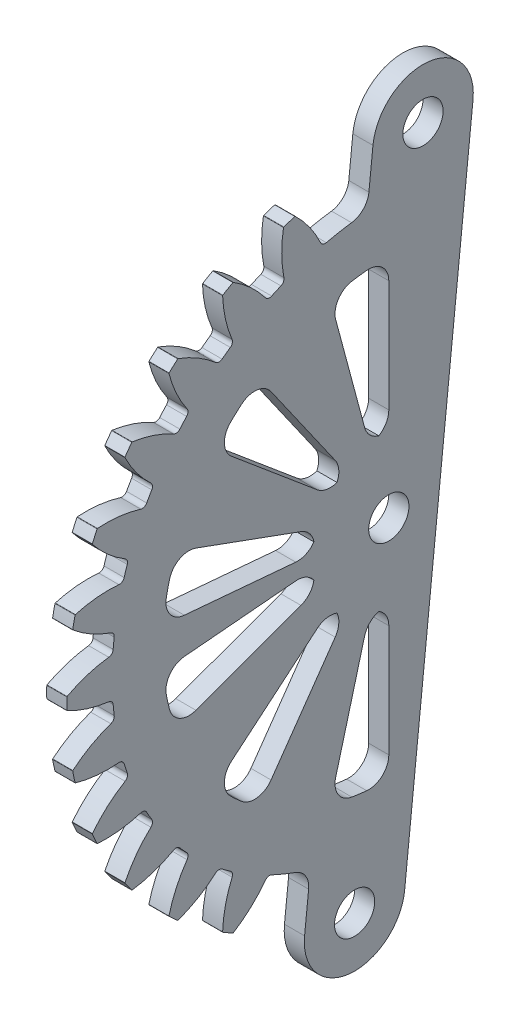
SolidWorks part; units mm, degrees
material "Thornel Mat VMA"
ref_plane "Plane1" through (0, 0, 0) normal (0, 0, 1) x (1, 0, 0)
ref_plane "Plane2" through (0, 0, 0) normal (0, 1, 0) x (1, 0, 0)
ref_plane "Plane3" through (0, 0, 0) normal (1, 0, 0) x (0, 0, -1)
sketch "HoldingSke" plane through (0, 0, 0) normal (0, 1, 0) x (1, 0, 0)
  line L0 (0, 0) -> (0.433, -0.25)
  line L1 (-15, 0) -> (100, 0) construction
  line L2 (0, 0) -> (-2.1039, 2.3779)
  line L3 (0, 0) -> (-11.863, 4.5341)
  line L4 (0, 0) -> (7.479, 4.318)
  line L5 (0, 0) -> (-46.8476, -17.4728)
  line L6 (0, 0) -> (-1.6579, -1.1186)
  line L7 (-2.1039, 2.3779) -> (8.6586, 51.2059)
  line L8 (-76.2, 54.61) -> (-76.1, 54.61)
  line L9 (-71.009, 38.7566) -> (-53.1078, 45.2721)
  line L10 (-76.2, 71.12) -> (104.1128, 71.12)
  line L11 (0, 0) -> (-2, 0)
  line L12 (-76.2, 101.6) -> (-76.133, 101.6)
  line L13 (24.9733, 27.94) -> (52.9518, 28.4284)
  line L14 (24.9733, 27.94) -> (24.9743, 27.94)
  line L15 (24.9733, 27.94) -> (100.4006, 29.5858)
  line L16 (-63.627, -2) -> (-12.827, -2)
  circle A0 centre (0, 0) radius 0.4
  circle A1 centre (0, 0) radius 27.499
  circle A2 centre (0, 0) radius 37.5
  circle A3 centre (0, 0) radius 0.4
  dimension "MHD" = 54.998
  dimension "Hub_dia" = 75
  dimension "Bore" = 0.8
  dimension "MBD" = 0.8
  dimension "Num_teeth" = 30
  dimension "Pitch" = 0.5
  dimension "Overall_len" = 50
  dimension "Show_teeth" = 30
  dimension "Thickness" = 2
  dimension "OAL" = 50.0001
  dimension "T_dim" = 0.1
  dimension "Ap" = 20
  dimension "H" = 19.05
  dimension "Pitch_radius" = 180.3128
  dimension "Width" = 2
  dimension "Backlash" = 0.067
  dimension "Addendum_fac" = 1
  dimension "Dedendum_fac" = 1.25
  dimension "Clearance_fac" = 0.25
  dimension "Dedendum_add" = 0.001
  dimension "Module" = 2
sketch "BasProSke" plane through (0, 0, 0) normal (0, 1, 0) x (1, 0, 0)
  line L0 (-10, 0) -> (60, 0) construction
  line L1 (0, 0) -> (0, 32)
  line L2 (0, 0) -> (2, 0)
  line L3 (2, 0) -> (2, 32)
  line L4 (2, 32) -> (0, 32)
  dimension "Thickness" = 2
  dimension "Diameter" = 64
revolve "Base-Revolve" add sketch "BasProSke" angle 360 about L0
sketch "TooCutSke" plane through (0, 0, 0) normal (1, 0, 0) x (0, 0, -1)
  line L1 (0, 0) -> (0, 107) construction
  line L2 (0, 0) -> (-1.6873, 29.9525) construction
  line L3 (0, 0) -> (-6.2643, 59.6013) construction
  line L4 (-1.6873, 29.9525) -> (-3.1322, 29.8007) construction
  arc A0 (0.9186, 27.4837) -> (-0.9186, 27.4837) centre (0, 0) ccw
  arc A1 (2.7618, 31.9061) -> (-2.7618, 31.9061) centre (0, 0) ccw
  circle A2 centre (0, 0) radius 30 construction
  circle A3 centre (0, 0) radius 28.1908 construction
  arc A4 (-0.9186, 27.4837) -> (-2.7618, 31.9061) centre (-12.6936, 25.1712) ccw
  arc A5 (2.7618, 31.9061) -> (0.9186, 27.4837) centre (12.6936, 25.1712) ccw
  dimension "Root_dia" = 54.998
  dimension "Overcut_dia" = 64.0508
  dimension "Pitch_dia" = 60
  dimension "Base_dia" = 56.3816
  dimension "Flank_rad" = 12
  dimension "Half_ang" = 6
  dimension "Half_CT" = 1.4528
extrude "ToothCut" cut sketch "TooCutSke" along normal through all
fillet "Breaks" radius 0.04 2 edges at (1, 31.882, -2.7455) (1, 31.882, 2.7455) tangent propagation no
fillet "RootFillets" radius 0.501 2 edges at (1, 27.4837, -0.9186) (1, 27.4837, 0.9186)
pattern_circular "TeethCuts" count 30 every 12 about axis through (-10, 0, 0) along (1, 0, 0) of "ToothCut", "RootFillets", "Breaks"
sketch "HubNeaOneSke" plane through (0, 0, 0) normal (-1, 0, 0) x (0, 0, 1)
  circle A0 centre (0, 0) radius 27.499
  dimension "Diameter" = 54.998
extrude "HubNearOne" [suppressed] add sketch "HubNeaOneSke" along normal blind 48.0001
sketch "HubNeaBotSke" plane through (0, 0, 0) normal (-1, 0, 0) x (0, 0, 1)
  circle A0 centre (0, 0) radius 27.499
  dimension "Diameter" = 54.998
extrude "HubNearBoth" [suppressed] add sketch "HubNeaBotSke" along normal blind 24
ref_plane "FarPln" through (2, 0, 0) normal (1, 0, 0) x (0, 0, -1)
sketch "HubFarSke" plane through (2, 0, 0) normal (1, 0, 0) x (0, 0, -1)
  circle A0 centre (0, 0) radius 27.499
  dimension "Diameter" = 54.998
extrude "HubFar" [suppressed] add sketch "HubFarSke" along normal blind 24
sketch "BorSke" plane through (0, 0, 0) normal (1, 0, 0) x (0, 0, -1)
  circle A0 centre (0, 0) radius 0.4
  dimension "Diameter" = 0.8
extrude "Bore" cut sketch "BorSke" along normal mid plane 100.0001
sketch "KeySke" plane through (0, 0, 0) normal (1, 0, 0) x (0, 0, -1)
  line L0 (-0.05, 0) -> (-0.05, 0.5)
  line L1 (-0.05, 0.5) -> (0.05, 0.5)
  line L2 (0.05, 0.5) -> (0.05, 0)
  line L3 (0, 0) -> (0, 34) construction
  line L4 (-0.05, 0) -> (0.05, 0)
  dimension "Offset" = 0.5
  dimension "Width" = 0.1
extrude "Keyway" [suppressed] cut sketch "KeySke" along normal mid plane 100.0001
pattern_circular "Keyway2" [suppressed] count 2 every 90 about axis through (-10, 0, 0) along (1, 0, 0)
sketch "草图1" plane through (2, 0, 0) normal (1, 0, 0) x (0, 0, -1)
  line L0 (3.3449, 31.8247) -> (-3.5838, -34.0978)
  line L1 (-3.5838, -34.0978) -> (46.0145, -34.9671)
  line L2 (46.0145, -34.9671) -> (40.1231, 36.265)
  line L3 (40.1231, 36.265) -> (5.1096, 33.8549)
  line L4 (5.1096, 33.8549) -> (3.3449, 31.8247)
  arc A0 (3.9197, 31.759) -> (2.769, 31.88) centre (0, 0) ccw construction
extrude "切除-拉伸1" cut sketch "草图1" against normal blind 10
sketch "草图2" plane through (2, 0, 0) normal (1, 0, 0) x (0, 0, -1)
  line L0 (-5.2209, 26.9988) -> (-4.9556, 33.126)
  line L1 (-4.9556, 33.126) -> (2.0931, 33.126)
  line L2 (0, 27.4942) -> (0.0018, 27.499)
  line L3 (2.0931, 33.126) -> (6.6978, 31.6646)
  line L4 (6.6978, 31.6646) -> (5.2159, 26.995)
  line L5 (-5.7192, -26.8928) -> (-5.7189, -26.8977)
  line L6 (-5.3088, -36.6799) -> (1.2342, -35.7971)
  line L7 (1.2342, -35.7971) -> (0, -27.4942)
  line L8 (-10.7202, -25.3234) -> (-14.1413, -34.6477)
  line L9 (-14.1413, -34.6477) -> (-5.3088, -36.6799)
  arc A0 (5.2159, 26.995) -> (0, 27.4942) centre (0, 0) ccw
  arc A3 (5.2173, 26.9995) -> (-5.2209, 26.9988) centre (0, 0) ccw
  arc A4 (-10.7202, -25.3234) -> (0.0007, -27.499) centre (0, 0) ccw
extrude "切除-拉伸3" cut sketch "草图2" against normal through all contours A3 L4 L3 L1 L0 | A4 L8 L9 L6 L7 region at (2, 30.1545, -0.3117) region at (2, -31.5853, 6.1529)
sketch "草图4" plane through (2, 0, 0) normal (1, 0, 0) x (0, 0, -1)
  line L1 (2.8744, 27.3484) -> (-2.8744, -27.3484)
  line L2 (2.8744, 27.3484) -> (7.847, 26.8257)
  line L3 (-2.8744, -27.3484) -> (2.0982, -27.871)
  line L4 (7.847, 26.8257) -> (2.0982, -27.871)
  dimension "D1" = 5
extrude "凸台-拉伸1" add sketch "草图4" against normal blind 2 contours L4 L3 L1 L2
sketch "草图5" plane through (2, 0, 0) normal (1, 0, 0) x (0, 0, -1)
  line L1 (0.0418, 0.3978) -> (-0.0418, -0.3978) construction
  circle A0 centre (0, 0) radius 2
  dimension "D1" = 4
extrude "切除-拉伸4" cut sketch "草图5" against normal blind 10
sketch "草图6" plane through (2, 0, 0) normal (1, 0, 0) x (0, 0, -1)
  line L0 (-3.9132, -37.2319) -> (3.9132, 37.2319) construction
  line L1 (7.847, 26.8257) -> (8.3697, 31.7983)
  line L2 (8.3697, 31.7983) -> (3.3971, 32.321) construction
  line L3 (-2.1461, 27.4151) -> (-1.5755, 32.8436)
  line L4 (2.8744, 27.3484) -> (7.847, 26.8257) construction
  line L5 (2.8744, 27.3484) -> (7.847, 26.8257)
  line L6 (0, 0) -> (9.8776, -1.0382) construction
  line L7 (1.5755, -32.8436) -> (-3.3971, -32.321) construction
  line L8 (-2.8744, -27.3484) -> (2.0982, -27.871)
  line L9 (-7.7991, -26.3698) -> (-8.3697, -31.7983)
  line L10 (2.0982, -27.871) -> (1.5755, -32.8436)
  arc A1 (8.3697, 31.7983) -> (-1.5755, 32.8436) centre (3.3971, 32.321) ccw
  arc A2 (2.8744, 27.3484) -> (-6.2119, 26.7882) centre (0, 0) ccw construction
  arc A3 (2.8744, 27.3484) -> (-2.1461, 27.4151) centre (0, 0) ccw
  arc A4 (-2.8744, -27.3484) -> (-7.7991, -26.3698) centre (0, 0) cw
  arc A5 (1.5755, -32.8436) -> (-8.3697, -31.7983) centre (-3.3971, -32.321) cw
  dimension "D1" = 5
  dimension "D2" = 5
extrude "凸台-拉伸2" add sketch "草图6" against normal blind 2
sketch "草图8" plane through (2, 0, 0) normal (1, 0, 0) x (0, 0, -1)
  line L0 (0, 0) -> (3.9197, 37.2936) construction
  line L1 (0, 0) -> (4.9726, -0.5226) construction
  line L2 (8.3697, 31.7983) -> (1.5755, -32.8436) construction
  arc A0 (8.3697, 31.7983) -> (-1.5755, 32.8436) centre (3.3971, 32.321) ccw construction
  circle A1 centre (3.3972, 32.322) radius 2
  circle A3 centre (-3.3972, -32.322) radius 2
  dimension "D1" = 4
  dimension "D2" = 32.5
extrude "切除-拉伸6" cut sketch "草图8" against normal blind 2
sketch "草图9" plane through (2, 0, 0) normal (1, 0, 0) x (0, 0, -1)
  line L0 (-46.0984, 0) -> (35.103, 0) construction
  line L1 (0, -7.5) -> (0, -22.5)
  line L2 (-1.9411, -7.2444) -> (-5.8234, -21.7333)
  line L3 (-4.3018, -6.1436) -> (-12.9055, -18.4309)
  line L4 (-5.7453, -4.8209) -> (-17.236, -14.4627)
  line L5 (-7.0477, -2.5652) -> (-21.1431, -7.6955)
  line L6 (-7.4715, -0.6537) -> (-22.4144, -1.961)
  line L7 (0, 0) -> (-5.8234, -21.7333) construction
  line L8 (0, 0) -> (-17.236, -14.4627) construction
  line L9 (0, 0) -> (-17.236, 14.4627) construction
  line L10 (0, 0) -> (-5.8234, 21.7333) construction
  line L11 (-7.4715, 0.6537) -> (-22.4144, 1.961)
  line L12 (-7.0477, 2.5652) -> (-21.1431, 7.6955)
  line L13 (-5.7453, 4.8209) -> (-17.236, 14.4627)
  line L14 (-4.3018, 6.1436) -> (-12.9055, 18.4309)
  line L15 (-1.9411, 7.2444) -> (-5.8234, 21.7333)
  line L16 (0, 7.5) -> (0, 22.5)
  arc A0 (-22.4144, -1.961) -> (-21.1431, -7.6955) centre (0, 0) ccw
  arc A1 (-7.4715, -0.6537) -> (-7.0477, -2.5652) centre (0, 0) ccw
  arc A2 (-17.236, -14.4627) -> (-12.9055, -18.4309) centre (0, 0) ccw
  arc A3 (-5.8234, -21.7333) -> (0, -22.5) centre (0, 0) ccw
  arc A4 (-1.9411, -7.2444) -> (0, -7.5) centre (0, 0) ccw
  arc A5 (-5.7453, -4.8209) -> (-4.3018, -6.1436) centre (0, 0) ccw
  arc A6 (-5.7453, 4.8209) -> (-4.3018, 6.1436) centre (0, 0) cw
  arc A7 (-1.9411, 7.2444) -> (0, 7.5) centre (0, 0) cw
  arc A8 (-5.8234, 21.7333) -> (0, 22.5) centre (0, 0) cw
  arc A9 (-17.236, 14.4627) -> (-12.9055, 18.4309) centre (0, 0) cw
  arc A10 (-7.4715, 0.6537) -> (-7.0477, 2.5652) centre (0, 0) cw
  arc A11 (-22.4144, 1.961) -> (-21.1431, 7.6955) centre (0, 0) cw
  dimension "D1" = 15
  dimension "D2" = 45
  dimension "D4" = 15
  dimension "D3" = 3
extrude "切除-拉伸7" cut sketch "草图9" against normal blind 10
fillet "圆角3" radius 2 26 edges at (1, -18.4309, 12.9055) (1, -14.4627, 17.236) (1, -4.8209, 5.7453) (1, -6.1436, 4.3018) (1, 7.5, 0) (1, 7.2444, 1.9411) (1, 21.7333, 5.8234) (1, 22.5, 0) (1, 6.1436, 4.3018) (1, 4.8209, 5.7453) (1, 14.4627, 17.236) (1, 18.4309, 12.9055) (1, -7.2444, 1.9411) (1, -7.5, 0) (1, -21.7333, 5.8234) (1, -7.6955, 21.1431) (1, -1.961, 22.4144) (1, -0.6537, 7.4715) (1, -2.5652, 7.0477) (1, 1.961, 22.4144) (1, 7.6955, 21.1431) (1, 2.5652, 7.0477) (1, 0.6537, 7.4715) (1, -22.5, 0) (1, 27.4151, 2.1461) (1, -26.3698, 7.7991)
equation "' \"Module@HoldingSke\" = 6.35"
equation "' \"Num_teeth@HoldingSke\" = 12"
equation "' \"Ap@HoldingSke\" =  20"
equation "' \"Ap@HoldingSke\" = 20"
equation "' \"Width@HoldingSke\" = 0.5 * 25.4"
equation "' \"Hub_dia@HoldingSke\"= 1 * 25.4"
equation "' \"Hub_dia@HoldingSke\" = 1 * 25.4"
equation "' \"Overall_len@HoldingSke\" = 1.0 * 25.4"
equation "' \"Bore@HoldingSke\" = 0.75 * 25.4"
equation "' \"T_dim@HoldingSke\" = 0.1 * 25.4"
equation "' \"Width@KeySke\" = 0.25 * 25.4"
equation "' \"Show_teeth@HoldingSke\" = 13"
equation "' \"Backlash@HoldingSke\" = 0.009 * 25.4"
equation "' \"Addendum_fac@HoldingSke\" = 1.0"
equation "' \"Dedendum_fac@HoldingSke\" = 1.25"
equation "' \"Dedendum_add@HoldingSke\" = 0.00005 * 25.4"
equation "' \"Clearance_fac@HoldingSke\" = 0.25"
equation "\"Pitch@HoldingSke\" = 1 / \"Module@HoldingSke\""
equation "\"Overcut_dia@TooCutSke\" = (\"Num_teeth@HoldingSke\" + 2 * \"Addendum_fac@HoldingSke\") / \"Pitch@HoldingSke\" + 0.002 * 25.4"
equation "\"Pitch_dia@TooCutSke\" = \"Num_teeth@HoldingSke\" / \"Pitch@HoldingSke\""
equation "\"Base_dia@TooCutSke\" = \"Num_teeth@HoldingSke\" / \"Pitch@HoldingSke\" * cos((\"Ap@HoldingSke\"  * 3.14159265 / 180))"
equation "\"Root_dia@TooCutSke\" = (\"Num_teeth@HoldingSke\" + 2) / \"Pitch@HoldingSke\" - 2 * (\"Addendum_fac@HoldingSke\" + \"Dedendum_fac@HoldingSke\") / \"Pitch@HoldingSke\" - \"Dedendum_add@HoldingSke\" * 2"
equation "\"Half_ang@TooCutSke\" = 180 / \"Num_teeth@HoldingSke\""
equation "\"Half_CT@TooCutSke\" = \"Num_teeth@HoldingSke\" / \"Pitch@HoldingSke\" * sin((3.14159265 / 2 / \"Num_teeth@HoldingSke\")) / 2 - 7 * \"Backlash@HoldingSke\" / 4"
equation "\"Flank_rad@TooCutSke\" = \"Num_teeth@HoldingSke\" / \"Pitch@HoldingSke\" / 5"
equation "\"Radius@RootFillets\" = \"Clearance_fac@HoldingSke\" / \"Pitch@HoldingSke\" + \"Dedendum_add@HoldingSke\""
equation "\"Break_rad@Breaks\" = 0.02 / \"Pitch@HoldingSke\""
equation "\"Thickness@HoldingSke\" = \"Width@HoldingSke\""
equation "\"OAL@HoldingSke\" = \"Thickness@HoldingSke\""
equation "\"MHD@HoldingSke\" = (\"Num_teeth@HoldingSke\" + 2) / \"Pitch@HoldingSke\" - 2 * (\"Addendum_fac@HoldingSke\" + \"Dedendum_fac@HoldingSke\")  / \"Pitch@HoldingSke\" - \"Dedendum_add@HoldingSke\" * 2"
equation "\"MBD@HoldingSke\" = (\"Num_teeth@HoldingSke\" + 2) / \"Pitch@HoldingSke\" - 2 * (\"Addendum_fac@HoldingSke\" + \"Dedendum_fac@HoldingSke\")  / \"Pitch@HoldingSke\" - \"Dedendum_add@HoldingSke\" * 2 - 0.002 * 25.4"
equation "\"MHD@HoldingSke\" = ((sgn( \"MHD@HoldingSke\" - \"Hub_dia@HoldingSke\" )-1)*( \"MHD@HoldingSke\" - \"Hub_dia@HoldingSke\" ))/-2+ \"Hub_dia@HoldingSke\""
equation "\"MBD@HoldingSke\" = ((sgn( \"MBD@HoldingSke\" - \"Bore@HoldingSke\" )-1)*( \"MBD@HoldingSke\" - \"Bore@HoldingSke\" ))/-2+ \"Bore@HoldingSke\""
equation "\"OAL@HoldingSke\" = ((sgn( \"OAL@HoldingSke\" - \"Overall_len@HoldingSke\" )+1)*( \"OAL@HoldingSke\" - \"Overall_len@HoldingSke\" ))/2 + \"Overall_len@HoldingSke\" + 0.000002 * 25.4"
equation "\"Num_teeth@TeethCuts\" = int( \"Show_teeth@HoldingSke\" ) + 1"
equation "\"Num_teeth@TeethCuts\" = ((sgn( \"Num_teeth@TeethCuts\" - \"Num_teeth@HoldingSke\" )-1)*( \"Num_teeth@TeethCuts\" - \"Num_teeth@HoldingSke\" ))/-2+ \"Num_teeth@HoldingSke\""
equation "\"Num_teeth@TeethCuts\" = ((sgn( \"Num_teeth@TeethCuts\" - 2.0)+1)*( \"Num_teeth@TeethCuts\" - 2.0))/2 +2.0"
equation "\"Angle@TeethCuts\" = 360.0 / \"Num_teeth@HoldingSke\""
equation "\"Diameter@BasProSke\" = (\"Num_teeth@HoldingSke\" + 2 * \"Addendum_fac@HoldingSke\") / \"Pitch@HoldingSke\""
equation "\"Thickness@BasProSke\"  = \"Thickness@HoldingSke\""
equation "' \"Fillet_rad@BasProSke\" =  \"Thickness@HoldingSke\" * 0.05"
equation "' \"Fillet_rad@BasProSke\" = \"Thickness@HoldingSke\" * 0.05"
equation "\"MHD@HoldingSke\" = ((sgn( \"MHD@HoldingSke\" - \"Root_dia@TooCutSke\" )-1)*( \"MHD@HoldingSke\" - \"Root_dia@TooCutSke\" ))/-2+ \"Root_dia@TooCutSke\""
equation "\"Diameter@HubNeaOneSke\" = \"MHD@HoldingSke\""
equation "\"Length@HubNearOne\" = \"OAL@HoldingSke\" - \"Thickness@BasProSke\""
equation "\"Diameter@HubNeaBotSke\" = \"MHD@HoldingSke\""
equation "\"Length@HubNearBoth\" = ( \"OAL@HoldingSke\" - \"Thickness@BasProSke\" ) / 2.0"
equation "\"Thickness@FarPln\" = \"Thickness@BasProSke\""
equation "\"Diameter@HubFarSke\" = \"MHD@HoldingSke\""
equation "\"Length@HubFar\" = ( \"OAL@HoldingSke\" - \"Thickness@BasProSke\" ) / 2.0"
equation "\"Diameter@BorSke\" = \"MBD@HoldingSke\""
equation "\"D1@Bore\" = \"OAL@HoldingSke\" * 2.0"
equation "\"D1@Keyway\" = \"OAL@HoldingSke\" * 2.0"
equation "\"Offset@KeySke\" = \"T_dim@HoldingSke\" + \"MBD@HoldingSke\" / 2.0"
